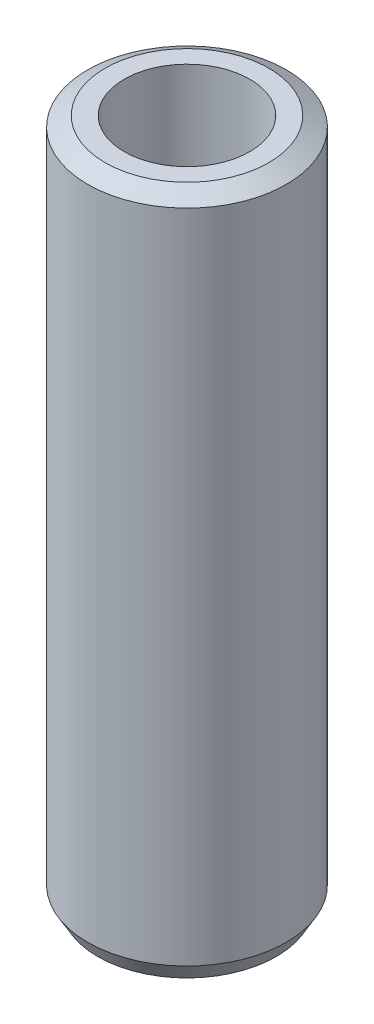
SolidWorks part; units mm, degrees
ref_plane "Front Plane" through (0, 0, 0) normal (0, 0, 1) x (1, 0, 0)
ref_plane "Top Plane" through (0, 0, 0) normal (0, 1, 0) x (1, 0, 0)
ref_plane "Right Plane" through (0, 0, 0) normal (1, 0, 0) x (0, 0, -1)
sketch "Sketch1" plane through (0, 0, 0) normal (0, 1, 0) x (1, 0, 0)
  circle A0 centre (0, 0) radius 42.5
  dimension "SHAFT_OD" = 85
extrude "Boss-Extrude1" add sketch "Sketch1" along normal blind 292.6547
sketch "Sketch2" plane through (0, 0, 0) normal (0, 1, 0) x (1, 0, 0)
  circle A0 centre (0, 0) radius 26.872
  dimension "BORE_D" = 53.7439
extrude "Cut-Extrude1" cut sketch "Sketch2" along normal through all
chamfer "Chamfer1" distance 4.3093 angle 60 2 edges at (0, 292.6547, 42.5) (0, 0, 42.5) first distance on face at (0, 292.6547, 42.5) first distance on face at (0, 0, 26.872)
